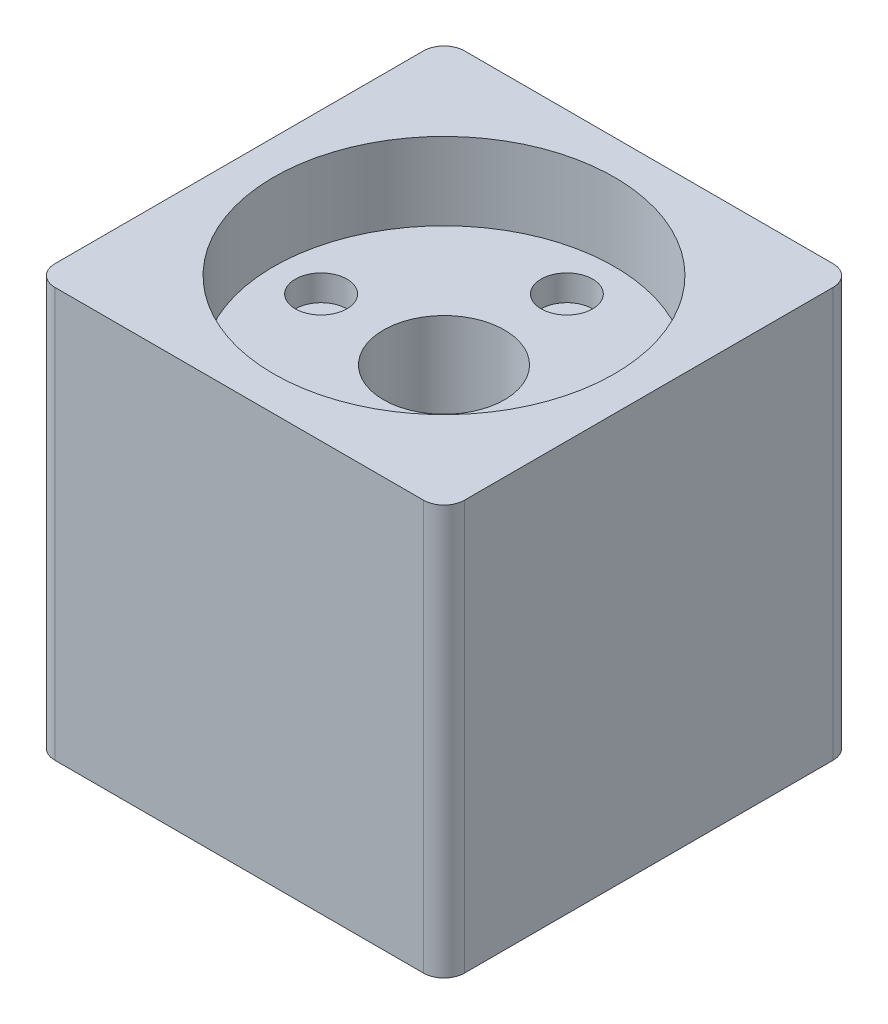
SolidWorks part; units mm, degrees
ref_plane "Front Plane" through (0, 0, 0) normal (0, 0, 1) x (1, 0, 0)
ref_plane "Top Plane" through (0, 0, 0) normal (0, 1, 0) x (1, 0, 0)
ref_plane "Right Plane" through (0, 0, 0) normal (1, 0, 0) x (0, 0, -1)
sketch "Sketch1" plane through (0, 0, 0) normal (0, 1, 0) x (1, 0, 0)
  line L1 (-1.5875, -1.5875) -> (1.5875, -1.5875) construction
  line L2 (-1.5875, -1.5875) -> (-1.5875, 1.5875) construction
  line L3 (-1.5875, 1.5875) -> (1.5875, 1.5875) construction
  line L4 (1.5875, -1.5875) -> (1.5875, 1.5875) construction
  line L5 (-1.5875, -1.5875) -> (1.5875, 1.5875) construction
  line L6 (-1.5875, 1.5875) -> (1.5875, -1.5875) construction
  line L7 (-7.9375, -7.9375) -> (7.9375, -7.9375)
  line L8 (-7.9375, -7.9375) -> (-7.9375, 7.9375)
  line L9 (-7.9375, 7.9375) -> (7.9375, 7.9375)
  line L10 (7.9375, -7.9375) -> (7.9375, 7.9375)
  line L11 (-7.9375, -7.9375) -> (7.9375, 7.9375) construction
  line L12 (-7.9375, 7.9375) -> (7.9375, -7.9375) construction
  circle A0 centre (0, 0) radius 2.2451 construction
  circle A1 centre (0, 0) radius 2.3451
  dimension "D1" = 3.175
  dimension "D3" = 15.875
  dimension "D2" = 0.1
extrude "Boss-Extrude1" add sketch "Sketch1" along normal mid plane 15.875
sketch "Sketch2" plane through (0, 7.9375, 0) normal (0, 1, 0) x (1, 0, 0)
  circle A0 centre (0, 0) radius 6.35 construction
  circle A1 centre (0, 0) radius 6.604
  dimension "D1" = 12.7
  dimension "D2" = 0.254
extrude "Cut-Extrude1" cut sketch "Sketch2" against normal blind 3
sketch "Sketch3" plane through (0, 4.9375, 0) normal (0, 1, 0) x (1, 0, 0)
  line L0 (0, 0) -> (-4.7625, 0) construction
  circle A0 centre (-4.7625, 0) radius 1
  dimension "D2" = 2
  dimension "D1" = 4.7625
extrude "Cut-Extrude2" cut sketch "Sketch3" against normal blind 1
ref_axis "Axis1" through (0, -8.7312, 0) along (0, 1, 0)
sketch "Sketch4" plane through (0, 0, 0) normal (0, 1, 0) x (1, 0, 0)
  circle A0 centre (0, 0) radius 11.1125
  dimension "D1" = 22.225
fillet "Fillet1" radius 0.7937 4 edges at (7.9375, 0, 7.9375) (7.9375, 0, -7.9375) (-7.9375, 0, 7.9375) (-7.9375, 0, -7.9375)
pattern_circular "CirPattern1" count 4 over 360 about axis through (0, -8.7312, 0) along (0, 1, 0) of "Cut-Extrude2"
equation "\"side_length\"=0.625"
equation "\"D1@Boss-Extrude1\"=\"side_length\""
